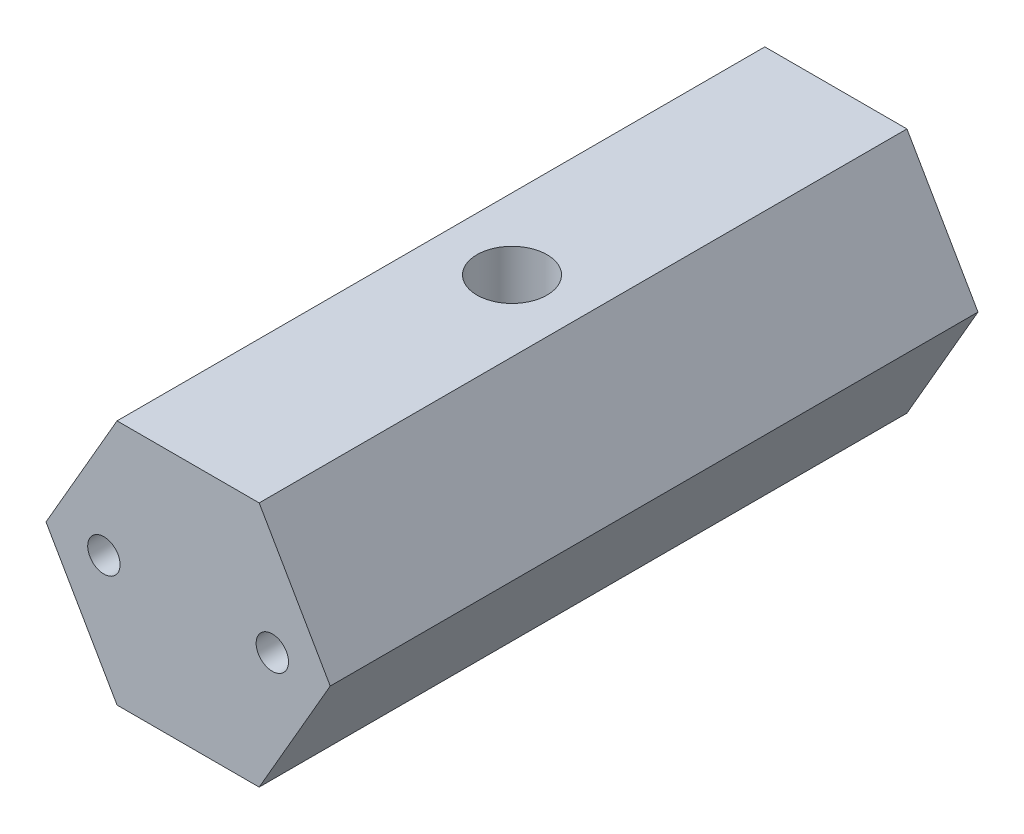
SolidWorks part; units mm, degrees
material "6061-T6 (SS)"
ref_plane "Front Plane" through (0, 0, 0) normal (0, 0, 1) x (1, 0, 0)
ref_plane "Top Plane" through (0, 0, 0) normal (0, 1, 0) x (1, 0, 0)
ref_plane "Right Plane" through (0, 0, 0) normal (1, 0, 0) x (0, 0, -1)
sketch "Sketch1" plane through (0, 0, 0) normal (0, 0, 1) x (1, 0, 0)
  line L1 (-5.4848, -9.5) -> (5.4848, -9.5)
  line L2 (5.4848, -9.5) -> (10.9697, 0)
  line L3 (10.9697, 0) -> (5.4848, 9.5)
  line L4 (5.4848, 9.5) -> (-5.4848, 9.5)
  line L5 (-5.4848, 9.5) -> (-10.9697, 0)
  line L6 (-10.9697, 0) -> (-5.4848, -9.5)
  circle A0 centre (0, 0) radius 9.5 construction
  circle A1 centre (-6.5, 0) radius 1.25
  circle A2 centre (-6.5, 0) radius 1.5 construction
  circle A3 centre (6.5, 0) radius 1.25
  circle A4 centre (6.5, 0) radius 1.5 construction
  point P20 (0, 0)
  dimension "D1" = 2.5
  dimension "D2" = 3
  dimension "D3" = 2
  dimension "D4" = 19
  dimension "D5" = 13
extrude "Boss-Extrude1" add sketch "Sketch1" along normal mid plane 50
sketch "Sketch2" plane through (0, 9.5, 0) normal (0, 1, 0) x (1, 0, 0)
  point P0 (0, 0)
hole_wizard "1/4-28 Tapped Hole1" positions "Sketch2" profile "Sketch3" tap size "1/4-28" standard "ANSI Inch" end condition up to next
cosmetic thread "Hole Thread1" parameters "D2"=6.35
sketch "Sketch3" plane through (0, 9.5, 0) normal (1, 0, 0) x (0, 0, 1)
  line L0 (0, 0) -> (0, 19)
  line L1 (0, 19) -> (2.7051, 19)
  line L2 (2.7051, 19) -> (2.7051, 0)
  line L5 (2.7051, 0) -> (0, 0)
  line L11 (0, -6.35) -> (0, 107.95) construction
  dimension "Thru Tap Drill Dia." = 5.4102
  dimension "Thru Tap Drill Depth" = 19
